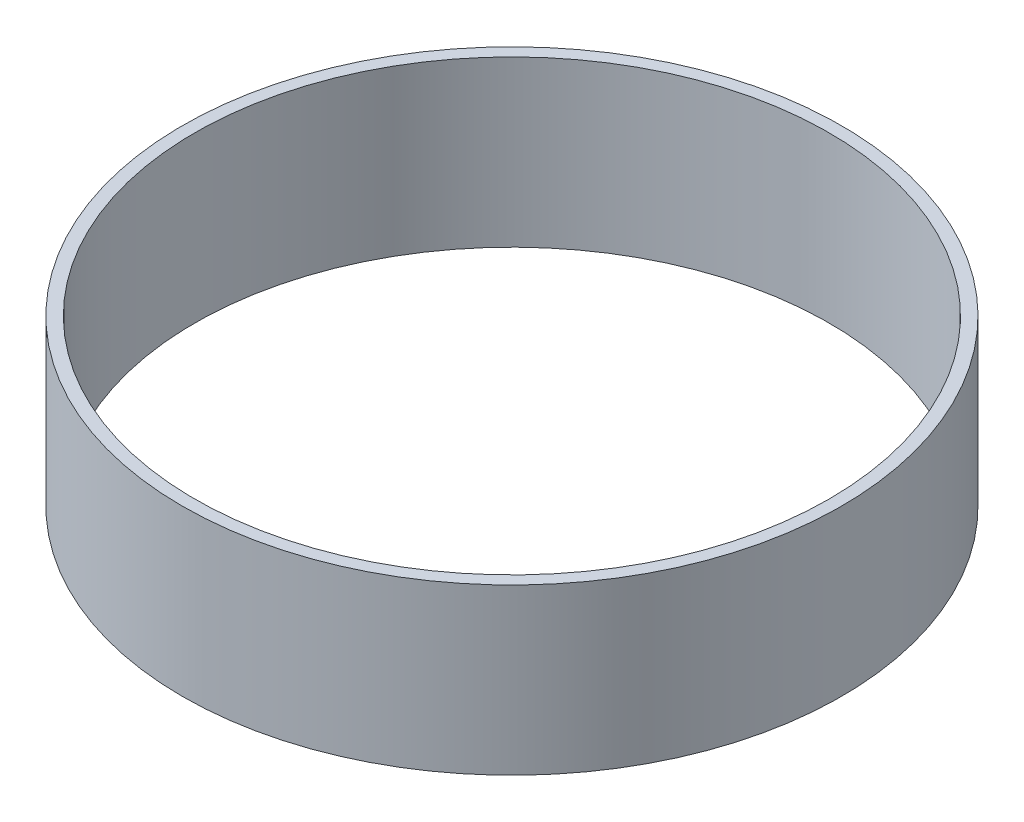
SolidWorks part; units mm, degrees
ref_plane "Спереди" through (0, 0, 0) normal (0, 0, 1) x (1, 0, 0)
ref_plane "Сверху" through (0, 0, 0) normal (0, 1, 0) x (1, 0, 0)
ref_plane "Справа" through (0, 0, 0) normal (1, 0, 0) x (0, 0, -1)
sketch "Эскиз1" plane through (0, 0, 0) normal (0, 1, 0) x (1, 0, 0)
  circle A0 centre (0, 0) radius 80
extrude "Вытянуть-Тонкостенный1" add sketch "Эскиз1" along normal blind 40 thin thin type one direction reverse wall 3
